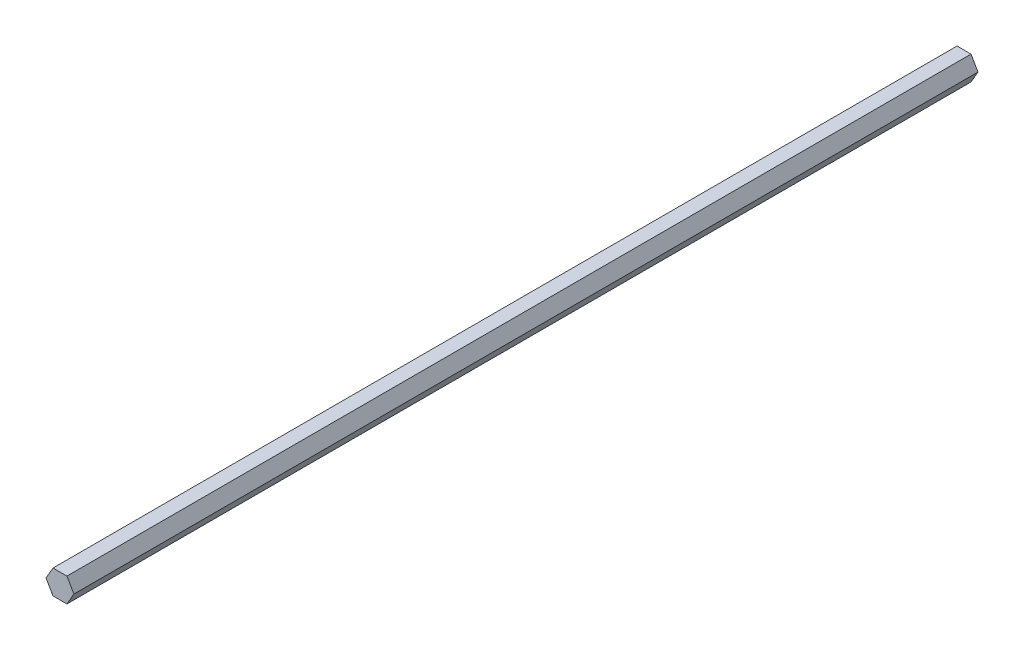
SolidWorks part; units mm, degrees
ref_plane "Front Plane" through (0, 0, 0) normal (0, 0, 1) x (1, 0, 0)
ref_plane "Top Plane" through (0, 0, 0) normal (0, 1, 0) x (1, 0, 0)
ref_plane "Right Plane" through (0, 0, 0) normal (1, 0, 0) x (0, 0, -1)
sketch "Sketch1" plane through (0, 0, 0) normal (0, 0, 1) x (1, 0, 0)
  line L1 (3.6662, -6.35) -> (7.3323, 0)
  line L2 (7.3323, 0) -> (3.6662, 6.35)
  line L3 (3.6662, 6.35) -> (-3.6662, 6.35)
  line L4 (-3.6662, 6.35) -> (-7.3323, 0)
  line L5 (-7.3323, 0) -> (-3.6662, -6.35)
  line L6 (-3.6662, -6.35) -> (3.6662, -6.35)
  circle A0 centre (0, 0) radius 6.35 construction
  dimension "D1" = 12.7
extrude "Boss-Extrude1" add sketch "Sketch1" along normal blind 475
